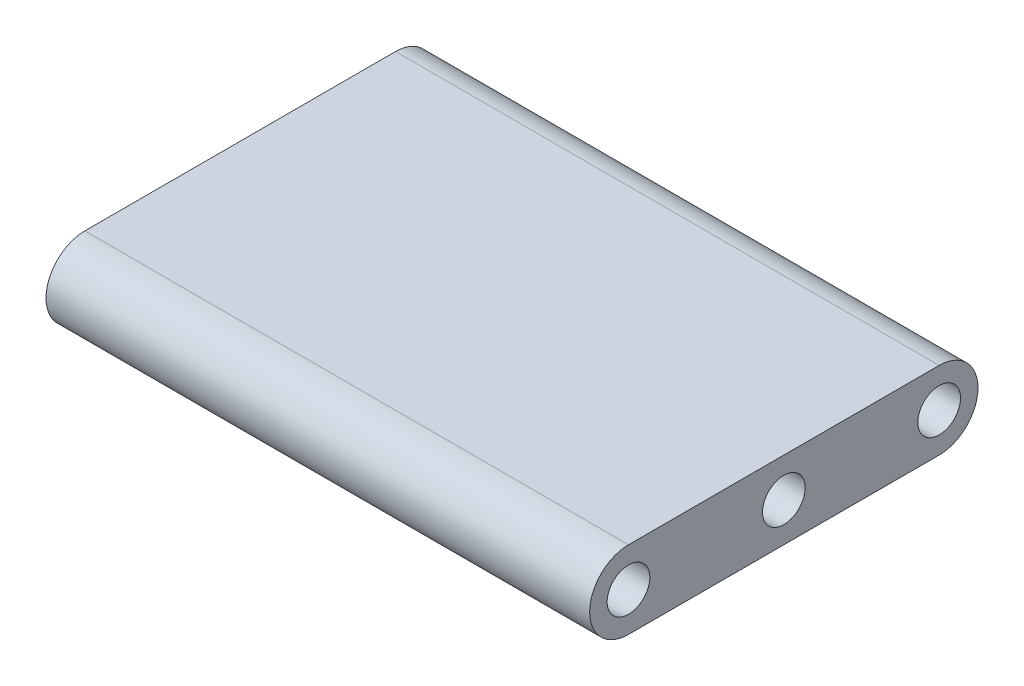
SolidWorks part; units mm, degrees
ref_plane "Front Plane" through (0, 0, 0) normal (0, 0, 1) x (1, 0, 0)
ref_plane "Top Plane" through (0, 0, 0) normal (0, 1, 0) x (1, 0, 0)
ref_plane "Right Plane" through (0, 0, 0) normal (1, 0, 0) x (0, 0, -1)
sketch "Sketch1" plane through (0, 0, 0) normal (1, 0, 0) x (0, 0, -1)
  line L1 (-25.4, -6.35) -> (25.4, -6.35)
  line L2 (-25.4, -6.35) -> (-25.4, 6.35) construction
  line L3 (-25.4, 6.35) -> (25.4, 6.35)
  line L4 (25.4, -6.35) -> (25.4, 6.35) construction
  line L5 (-25.4, -6.35) -> (25.4, 6.35) construction
  line L6 (-25.4, 6.35) -> (25.4, -6.35) construction
  circle A0 centre (-25.4, 0) radius 3.4925
  arc A1 (-25.4, 6.35) -> (-25.4, -6.35) centre (-25.4, 0) ccw
  circle A2 centre (25.4, 0) radius 3.4925
  arc A3 (25.4, -6.35) -> (25.4, 6.35) centre (25.4, 0) ccw
  circle A4 centre (0, 0) radius 3.4925
  point P0 (0, 0)
  dimension "D3" = 6.985
  dimension "D4" = 12.7
  dimension "D1" = 12.7
  dimension "D2" = 50.8
extrude "Boss-Extrude1" add sketch "Sketch1" along normal mid plane 88.9 contours L3 A1 L1 A0 | A2 L3 A0 L1 | L1 A3 L3 A2 region at (0, 0, 31.1024)
